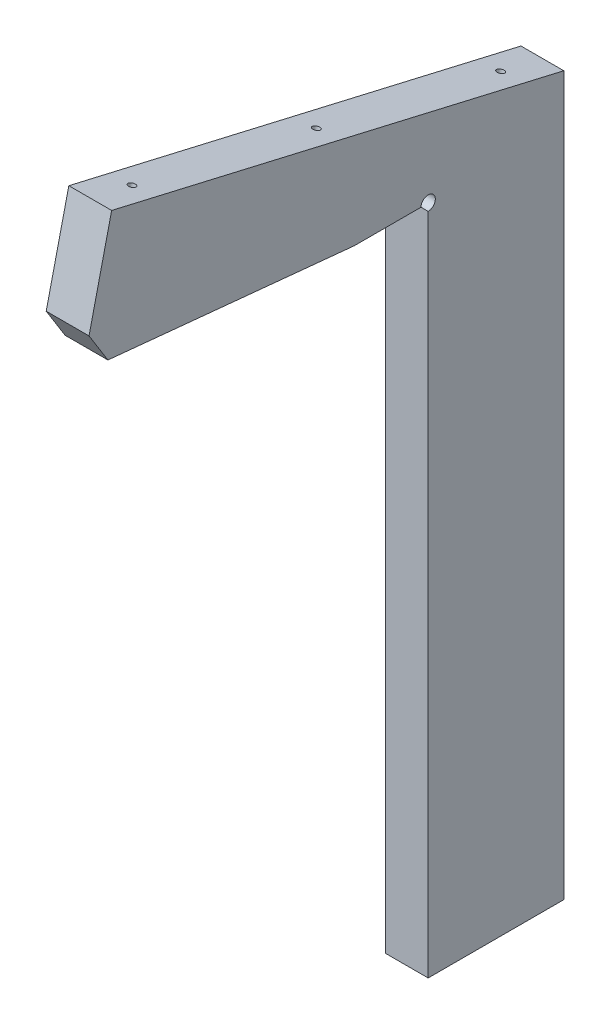
SolidWorks part; units mm, degrees
material "MDF"
ref_plane "Front Plane" through (0, 0, 0) normal (0, 0, 1) x (1, 0, 0)
ref_plane "Top Plane" through (0, 0, 0) normal (0, 1, 0) x (1, 0, 0)
ref_plane "Right Plane" through (0, 0, 0) normal (1, 0, 0) x (0, 0, -1)
sketch "Sketch2" plane through (-113.7888, 0, 0) normal (1, 0, 0) x (0, 0, -1)
  line L17 (0, 20.8246) -> (-83.8286, 40.3069)
  line L18 (0, 20.8246) -> (-83.8286, 40.3069)
  line L29 (-83.8286, 40.3069) -> (-93.1962, 0)
  line L30 (-83.8286, 40.3069) -> (-93.1962, 0)
  line L31 (-93.1962, 0) -> (-63.5, 0)
  line L32 (-93.1962, 0) -> (-63.5, 0)
  line L46 (0, -298.45) -> (-60.325, -298.45)
  line L47 (0, -392.9838) -> (0, -398.937) construction
  line L48 (-28.575, -298.45) -> (0, -298.45) construction
  line L53 (-8.8658, -437.642) -> (0, -437.642)
  line L55 (0, -437.642) -> (0, 20.8246)
  line L57 (-60.325, -3.175) -> (-60.325, -412.75)
  line L60 (0, -298.45) -> (0, 20.8246)
  line L62 (-60.325, -3.175) -> (-60.325, -298.45)
  arc A14 (-60.325, -3.175) -> (-63.5, 0) centre (-60.325, 0) ccw
  arc A15 (-60.325, -412.75) -> (-8.8658, -437.642) centre (-28.575, -412.75) ccw
  arc A17 (-60.325, -3.175) -> (-63.5, 0) centre (-60.325, 0) ccw
  dimension "D2" = 0
extrude "Boss-Extrude1" add sketch "Sketch2" along normal blind 19.05
sketch "Sketch3" plane through (-113.7888, 0, 0) normal (-1, 0, 0) x (0, 0, 1)
  line L0 (83.8286, 40.3069) -> (201.0857, 67.5582)
  line L1 (495.3358, 135.9439) -> (66.675, 36.3203) construction
  line L2 (201.0857, 67.5582) -> (214.0229, 11.8918)
  line L7 (83.8286, 40.3069) -> (93.1962, 0)
  line L8 (93.1962, 0) -> (214.0229, 11.8918)
  arc A0 (63.5, 0) -> (60.325, -3.175) centre (60.325, 0) ccw construction
  dimension "D1" = 57.15
  dimension "D2" = 152.4
extrude "Boss-Extrude2" add sketch "Sketch3" against normal through all
chamfer "Chamfer1" distance 12.7 angle 45 1 edges at (-104.2638, 11.8918, 214.0229) first distance on face at (-104.2638, 39.725, 207.5543)
hole_wizard "Hole3" positions "Sketch8" profile "Sketch9" legacy
sketch "Sketch8" plane through (0, 45.0826, -35.8775) normal (0, 0.974, -0.2264) x (-1, 0, 0)
  line L0 (218.5638, 29.4548) -> (218.5638, 115.5175) construction
  line L4 (202.6895, 537.9919) -> (202.6895, 97.9067) construction
  line L9 (88.3895, 537.9919) -> (88.3895, 97.9067) construction
  line L13 (104.2638, 29.4548) -> (104.2638, 235.8996) construction
  line L16 (0, 537.9919) -> (0, 29.4548) construction
  point P0 (218.5638, 102.8175)
  point P2 (218.5638, 48.5048)
  point P33 (202.6895, 123.3067)
  point P35 (202.6895, 317.9493)
  point P37 (202.6895, 518.9419)
  point P51 (88.3895, 518.9419)
  point P53 (88.3895, 317.9493)
  point P55 (88.3895, 123.3067)
  point P69 (104.2638, 216.8496)
  point P71 (104.2638, 132.6772)
  point P73 (104.2638, 48.5048)
  point P83 (-104.2638, 48.5048)
  point P84 (-104.2638, 132.6772)
  point P85 (-104.2638, 216.8496)
  point P86 (-88.3895, 123.3067)
  point P87 (-88.3895, 317.9493)
  point P88 (-88.3895, 518.9419)
  point P89 (-202.6895, 518.9419)
  point P90 (-202.6895, 317.9493)
  point P91 (-202.6895, 123.3067)
  point P92 (-218.5638, 48.5048)
  point P93 (-218.5638, 102.8175)
sketch "Sketch9" plane through (-218.5638, 68.3578, 64.2709) normal (1, 0, 0) x (0, 0.2264, 0.974)
  line L0 (0, 0) -> (0, 51.7539)
  line L1 (0, 51.7539) -> (1.5875, 50.8)
  line L2 (1.5875, 50.8) -> (1.5875, 4.0177)
  line L3 (1.5875, 4.0177) -> (5.08, 0)
  line L4 (5.08, 0) -> (0, 0)
  line L5 (0, -14.3089) -> (0, 102.4216) construction
  line L6 (0, 51.7539) -> (-1.5875, 50.8) construction
  line L7 (-1.5875, 4.0177) -> (-5.08, 0) construction
  dimension "Diameter" = 3.175
  dimension "Depth" = 50.8
  dimension "C-Sink Diameter" = 10.16
  dimension "C-Sink Angle" = 82
  dimension "Drill Angle" = 118
hole_wizard "Hole4" positions "Sketch10" profile "Sketch11" legacy
sketch "Sketch10" plane through (0, 0, -25.4) normal (0, 0, -1) x (-1, 0, 0)
  line L0 (218.5638, 0) -> (218.5638, -437.642) construction
  line L4 (104.2638, 0) -> (104.2638, -298.45) construction
  line L13 (120.1388, -463.55) -> (120.1388, -311.15) construction
  line L16 (126.4888, -311.15) -> (113.7888, -311.15) construction
  line L18 (126.4888, -304.8) -> (-126.4888, -304.8) construction
  line L22 (94.7388, -276.225) -> (-94.7388, -276.225) construction
  line L24 (-94.7388, -285.75) -> (-94.7388, -266.7) construction
  line L26 (94.7388, -285.75) -> (94.7388, -266.7) construction
  line L27 (-94.7388, 0) -> (-94.7388, -19.05) construction
  line L29 (94.7388, 0) -> (94.7388, -19.05) construction
  line L31 (94.7388, -9.525) -> (-94.7388, -9.525) construction
  point P15 (218.5638, -31.75)
  point P17 (218.5638, -218.821)
  point P19 (218.5638, -418.592)
  point P28 (104.2638, -19.05)
  point P30 (104.2638, -149.225)
  point P32 (104.2638, -279.4)
  point P69 (120.1388, -330.2)
  point P71 (120.1388, -444.5)
  point P76 (-120.1388, -444.5)
  point P77 (-120.1388, -330.2)
  point P80 (-104.2638, -279.4)
  point P81 (-104.2638, -149.225)
  point P82 (-104.2638, -19.05)
  point P83 (-218.5638, -418.592)
  point P84 (-218.5638, -218.821)
  point P85 (-218.5638, -31.75)
  point P99 (0, -304.8)
  point P101 (107.4388, -304.8)
  point P103 (-107.4388, -304.8)
  point P127 (75.6888, -276.225)
  point P129 (0, -276.225)
  point P131 (-75.6888, -276.225)
  point P152 (75.6888, -9.525)
  point P154 (0, -9.525)
  point P156 (-75.6888, -9.525)
sketch "Sketch11" plane through (75.6888, -9.525, -25.4) normal (1, 0, 0) x (0, 1, 0)
  line L0 (0, 0) -> (0, 39.0539)
  line L1 (0, 39.0539) -> (1.5875, 38.1)
  line L2 (1.5875, 38.1) -> (1.5875, 4.0177)
  line L3 (1.5875, 4.0177) -> (5.08, 0)
  line L4 (5.08, 0) -> (0, 0)
  line L5 (0, -14.3089) -> (0, 102.4216) construction
  line L6 (0, 39.0539) -> (-1.5875, 38.1) construction
  line L7 (-1.5875, 4.0177) -> (-5.08, 0) construction
  dimension "Diameter" = 3.175
  dimension "Depth" = 38.1
  dimension "C-Sink Diameter" = 10.16
  dimension "C-Sink Angle" = 82
  dimension "Drill Angle" = 118
